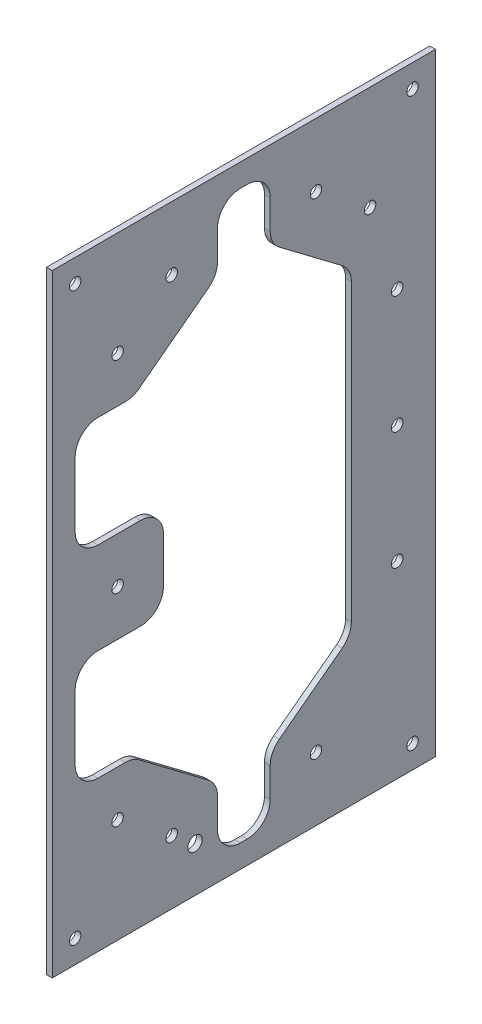
SolidWorks part; units mm, degrees
material "6061-T6 (SS)"
ref_plane "Front Plane" through (0, 0, 0) normal (0, 0, 1) x (1, 0, 0)
ref_plane "Top Plane" through (0, 0, 0) normal (0, 1, 0) x (1, 0, 0)
ref_plane "Right Plane" through (0, 0, 0) normal (1, 0, 0) x (0, 0, -1)
sketch "Sketch1" plane through (0, 0, 0) normal (1, 0, 0) x (0, 0, -1)
  line L0 (0, -169.8625) -> (212.5, -169.8625) construction
  line L1 (0, 0) -> (212.5, 0)
  line L2 (0, 0) -> (0, -339.725)
  line L3 (0, -339.725) -> (212.5, -339.725)
  line L4 (212.5, 0) -> (212.5, -339.725)
  line L5 (153.5, -35.2425) -> (59, -35.2425) construction
  line L6 (191.25, -104.5325) -> (191.25, -169.8625) construction
  line L7 (13.5, -50.2425) -> (59, -50.2425) construction
  line L8 (36.25, -50.2425) -> (36.25, -169.8625) construction
  line L9 (106.25, 0) -> (106.25, -339.725) construction
  line L10 (173.5, -104.5325) -> (191.25, -104.5325) construction
  circle A0 centre (12.7, -12.7) radius 3.175
  circle A1 centre (199.8, -12.7) radius 3.175
  circle A2 centre (66.25, -35.2425) radius 3.175
  circle A3 centre (146.25, -35.2425) radius 3.175
  circle A4 centre (176.25, -57.8625) radius 3.175
  circle A5 centre (36.25, -57.8625) radius 3.175
  circle A6 centre (191.25, -104.5325) radius 3.175
  circle A7 centre (36.25, -169.8625) radius 3.175
  circle A8 centre (191.25, -169.8625) radius 3.175
  circle A9 centre (36.25, -281.8625) radius 3.175
  circle A10 centre (66.25, -304.4825) radius 3.175
  circle A11 centre (12.7, -327.025) radius 3.175
  circle A12 centre (199.8, -327.025) radius 3.175
  circle A13 centre (146.25, -304.4825) radius 3.175
  circle A14 centre (191.25, -235.1925) radius 3.175
  dimension "D1" = 339.725
  dimension "D2" = 212.5
  dimension "D3" = 40
  dimension "D4" = 112
  dimension "D5" = 85
  dimension "D6" = 157.1625
extrude "Boss-Extrude1" add sketch "Sketch1" along normal blind 3.175
sketch "Sketch2" plane through (3.175, 0, 0) normal (1, 0, 0) x (0, 0, -1)
  line L1 (165.85, -88.1617) -> (165.85, -251.5633)
  line L4 (0, 0) -> (0, -339.725)
  line L5 (0, -339.725) -> (212.5, -339.725)
  line L6 (212.5, -339.725) -> (212.5, 0)
  line L7 (212.5, 0) -> (0, 0)
  line L8 (0, 0) -> (0, -339.725)
  line L9 (0, -339.725) -> (212.5, -339.725)
  line L10 (212.5, -339.725) -> (212.5, 0)
  line L11 (212.5, 0) -> (0, 0)
  line L14 (25.4, -144.4625) -> (48.95, -144.4625)
  line L15 (25.4, -83.2625) -> (40.5014, -83.2625)
  line L16 (12.7, -95.9625) -> (12.7, -131.7625)
  line L17 (34.7163, -60.6425) -> (37.7837, -60.6425)
  line L18 (61.65, -70.5625) -> (61.65, -70.522)
  line L19 (61.65, -182.5625) -> (61.65, -157.1625)
  line L20 (36.25, -57.8625) -> (66.25, -35.2425) construction
  line L21 (48.1473, -80.703) -> (86.5959, -51.7127)
  line L22 (91.65, -25.4) -> (91.65, -41.5722)
  line L23 (120.85, -25.4) -> (120.85, -41.5722)
  line L24 (104.35, -12.7) -> (108.15, -12.7)
  line L25 (176.25, -57.8625) -> (146.25, -35.2425) construction
  line L26 (125.9041, -51.7127) -> (160.7959, -78.0212)
  line L27 (0, -169.8625) -> (212.5, -169.8625) construction
  line L28 (176.25, -281.8625) -> (146.25, -304.4825) construction
  line L29 (36.25, -281.8625) -> (66.25, -304.4825) construction
  line L30 (125.9041, -288.0123) -> (160.7959, -261.7038)
  line L31 (104.35, -327.025) -> (108.15, -327.025)
  line L32 (120.85, -314.325) -> (120.85, -298.1528)
  line L33 (91.65, -314.325) -> (91.65, -298.1528)
  line L34 (48.1473, -259.022) -> (86.5959, -288.0123)
  line L35 (61.65, -269.1625) -> (61.65, -269.203)
  line L36 (34.7163, -279.0825) -> (37.7837, -279.0825)
  line L37 (12.7, -243.7625) -> (12.7, -207.9625)
  line L38 (25.4, -256.4625) -> (40.5014, -256.4625)
  line L39 (25.4, -195.2625) -> (48.95, -195.2625)
  circle A0 centre (176.25, -57.8625) radius 3.175 construction
  circle A1 centre (146.25, -35.2425) radius 3.175 construction
  circle A2 centre (66.25, -35.2425) radius 3.175 construction
  circle A3 centre (36.25, -57.8625) radius 3.175 construction
  circle A4 centre (36.25, -169.8625) radius 3.175 construction
  circle A5 centre (36.25, -281.8625) radius 3.175 construction
  circle A6 centre (66.25, -304.4825) radius 3.175 construction
  circle A7 centre (146.25, -304.4825) radius 3.175 construction
  circle A8 centre (191.25, -235.1925) radius 3.175 construction
  circle A9 centre (191.25, -169.8625) radius 3.175 construction
  circle A10 centre (191.25, -104.5325) radius 3.175 construction
  circle A11 centre (176.25, -57.8625) radius 3.175 construction
  circle A12 centre (146.25, -35.2425) radius 3.175 construction
  circle A13 centre (66.25, -35.2425) radius 3.175 construction
  circle A14 centre (36.25, -57.8625) radius 3.175 construction
  circle A15 centre (36.25, -169.8625) radius 3.175 construction
  circle A16 centre (36.25, -281.8625) radius 3.175 construction
  circle A17 centre (66.25, -304.4825) radius 3.175 construction
  circle A18 centre (146.25, -304.4825) radius 3.175 construction
  circle A19 centre (191.25, -235.1925) radius 3.175 construction
  circle A20 centre (191.25, -169.8625) radius 3.175 construction
  circle A21 centre (191.25, -104.5325) radius 3.175 construction
  arc A28 (48.95, -144.4625) -> (61.65, -157.1625) centre (48.95, -157.1625) cw
  arc A29 (12.7, -131.7625) -> (25.4, -144.4625) centre (25.4, -131.7625) ccw
  arc A30 (12.7, -95.9625) -> (25.4, -83.2625) centre (25.4, -95.9625) cw
  arc A33 (165.85, -88.1617) -> (160.7959, -78.0212) centre (153.15, -88.1617) ccw
  arc A34 (125.9041, -51.7127) -> (120.85, -41.5722) centre (133.55, -41.5722) cw
  arc A35 (108.15, -12.7) -> (120.85, -25.4) centre (108.15, -25.4) cw
  arc A36 (104.35, -12.7) -> (91.65, -25.4) centre (104.35, -25.4) ccw
  arc A37 (86.5959, -51.7127) -> (91.65, -41.5722) centre (78.95, -41.5722) ccw
  arc A38 (48.1473, -80.703) -> (40.5014, -83.2625) centre (40.5014, -70.5625) cw
  circle A39 centre (36.25, -281.8625) radius 3.175 construction
  circle A40 centre (66.25, -304.4825) radius 3.175 construction
  circle A41 centre (146.25, -304.4825) radius 3.175 construction
  circle A42 centre (176.25, -281.8625) radius 3.175 construction
  arc A43 (48.1473, -259.022) -> (40.5014, -256.4625) centre (40.5014, -269.1625) ccw
  arc A44 (86.5959, -288.0123) -> (91.65, -298.1528) centre (78.95, -298.1528) cw
  arc A45 (104.35, -327.025) -> (91.65, -314.325) centre (104.35, -314.325) cw
  arc A46 (108.15, -327.025) -> (120.85, -314.325) centre (108.15, -314.325) ccw
  arc A47 (125.9041, -288.0123) -> (120.85, -298.1528) centre (133.55, -298.1528) ccw
  arc A48 (165.85, -251.5633) -> (160.7959, -261.7038) centre (153.15, -251.5633) cw
  arc A49 (12.7, -243.7625) -> (25.4, -256.4625) centre (25.4, -243.7625) ccw
  arc A50 (12.7, -207.9625) -> (25.4, -195.2625) centre (25.4, -207.9625) cw
  arc A51 (48.95, -195.2625) -> (61.65, -182.5625) centre (48.95, -182.5625) ccw
  point P73 (61.65, -83.2625)
  point P78 (61.65, -60.6425)
  point P92 (61.65, -279.0825)
  point P110 (61.65, -169.8625)
  point P114 (165.85, -169.8625)
  point P115 (61.65, -256.4625)
  dimension "D11" = 25.4
  dimension "D13" = 25.4
  dimension "D17" = 12.7
  dimension "D2" = 25.4
  dimension "D7" = 25.4
  dimension "D8" = 25.4
  dimension "D9" = 25.4
  dimension "D14" = 25.4
  dimension "D15" = 12.7
  dimension "D16" = 25.4
  dimension "D1" = 0
extrude "Cut-Extrude1" cut sketch "Sketch2" against normal through all contours L1 L18 L15 A30 L16 A29 L14 A28 L19 A43 region at (3.175, -169.8625, -97.6088)
sketch "Sketch3" plane through (0, 0, 0) normal (-1, 0, 0) x (0, 0, 1)
  line L0 (-212.5, -339.725) -> (-79.15, -339.725)
  line L1 (0, -339.725) -> (-212.5, -339.725) construction
  line L2 (-79.15, -339.725) -> (-79.15, -314.725)
  line L3 (-212.5, 0) -> (-83.8431, 0)
  line L4 (-212.5, 0) -> (0, 0) construction
  circle A0 centre (-79.15, -314.725) radius 4
  dimension "D4" = 8
  dimension "D1" = 133.35
  dimension "D2" = 25
  dimension "D3" = 128.6569
extrude "Cut-Extrude2" cut sketch "Sketch3" against normal blind 13.97 contours A0 region at (0, -317.4734, -76.4016)
sketch "Sketch4" plane through (0, 0, 0) normal (-1, 0, 0) x (0, 0, 1)
  circle A0 centre (-66.25, -304.4825) radius 3.175 construction
  circle A1 centre (-79.15, -314.725) radius 4 construction
  circle A2 centre (-66.25, -304.4825) radius 3.175
  circle A3 centre (-79.15, -314.725) radius 4
